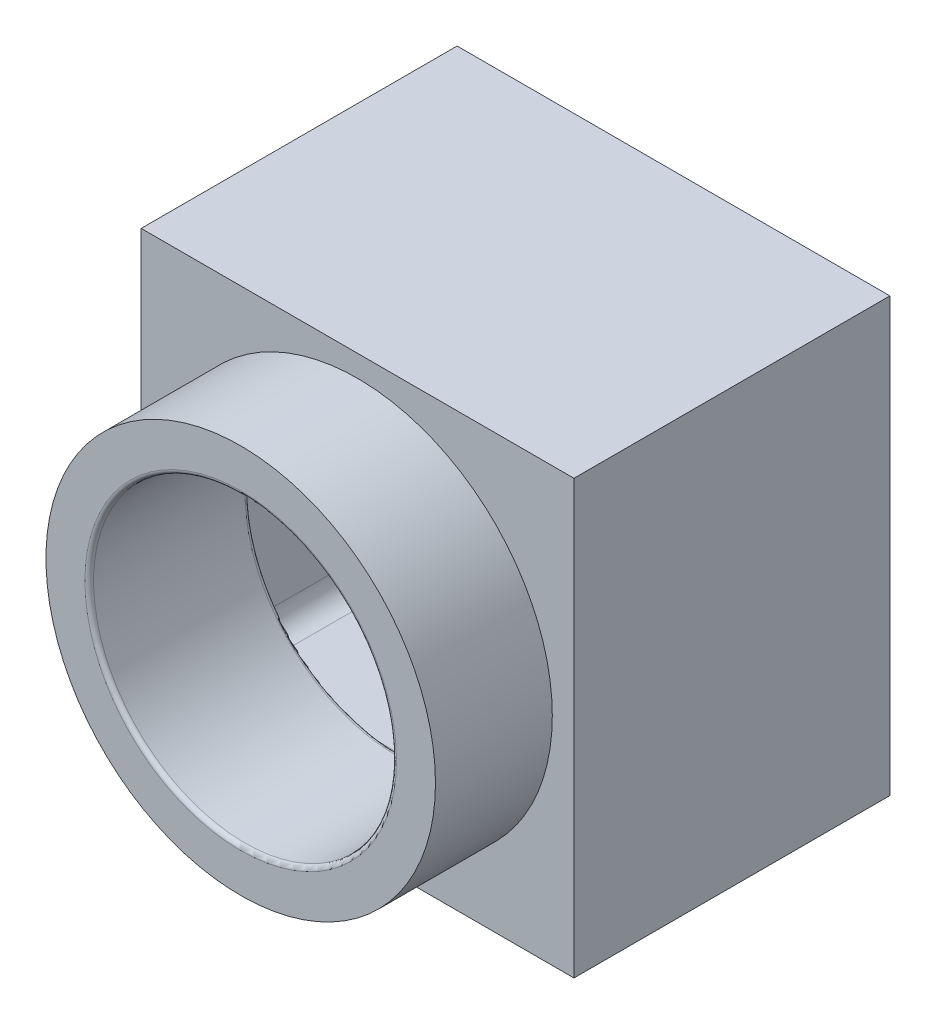
SolidWorks part; units mm, degrees
ref_plane "Front Plane" through (0, 0, 0) normal (0, 0, 1) x (1, 0, 0)
ref_plane "Top Plane" through (0, 0, 0) normal (0, 1, 0) x (1, 0, 0)
ref_plane "Right Plane" through (0, 0, 0) normal (1, 0, 0) x (0, 0, -1)
sketch "Sketch1" plane through (0, 0, 0) normal (0, 0, 1) x (1, 0, 0)
  line L1 (-12.7, 12.7) -> (12.7, 12.7)
  line L2 (-12.7, 12.7) -> (-12.7, -12.7)
  line L3 (-12.7, -12.7) -> (12.7, -12.7)
  line L4 (12.7, 12.7) -> (12.7, -12.7)
  line L5 (-12.7, 12.7) -> (12.7, -12.7) construction
  dimension "D1" = 25.4
  dimension "D2" = 25.4
extrude "Boss-Extrude1" add sketch "Sketch1" against normal blind 25.4
ref_plane "Plane1" through (0, 0, -9.398) normal (0, 0, 1) x (1, 0, 0)
sketch "Sketch2" plane through (0, 0, -9.398) normal (0, 0, 1) x (1, 0, 0)
  line L0 (-11.2268, 10.2235) -> (11.2268, -10.2235) construction
  line L1 (-11.2268, 10.2235) -> (11.2268, 10.2235)
  line L2 (-11.2268, 10.2235) -> (-11.2268, -10.2235)
  line L3 (-11.2268, -10.2235) -> (11.2268, -10.2235)
  line L4 (11.2268, 10.2235) -> (11.2268, -10.2235)
  point P4 (0, 0)
  dimension "D1" = 22.4536
  dimension "D2" = 20.447
extrude "Cut-Extrude1" cut sketch "Sketch2" against normal through all
sketch "Sketch3" plane through (0, 0, 0) normal (0, 0, 1) x (1, 0, 0)
  circle A0 centre (0, 0) radius 8.89
  dimension "D1" = 17.78
extrude "Cut-Extrude2" cut sketch "Sketch3" against normal through all both and the other way through all
ref_plane "Plane2" through (0, 0, -6.858) normal (0, 0, 1) x (1, 0, 0)
sketch "Sketch4" plane through (0, 0, -6.858) normal (0, 0, 1) x (1, 0, 0)
  circle A0 centre (0, 0) radius 8.89 construction
  circle A1 centre (0, 0) radius 8.89 construction
  circle A2 centre (0, 0) radius 11.43
  circle A3 centre (0, 0) radius 63.5
  dimension "D2" = 127
  dimension "D1" = 2.54
extrude "Cut-Extrude3" cut sketch "Sketch4" along normal through all
fillet "Fillet1" radius 1.27 4 edges at (0, -10.2235, -9.398) (11.2268, 0, -9.398) (0, 10.2235, -9.398) (-11.2268, 0, -9.398)
fillet "Fillet2" radius 1.27 8 edges at (-10.8548, -9.8515, -9.77) (-10.8548, 9.8515, -9.77) (10.8548, 9.8515, -9.77) (10.8548, -9.8515, -9.77) (-11.2268, -10.2235, -18.034) (-11.2268, 10.2235, -18.034) (11.2268, 10.2235, -18.034) (11.2268, -10.2235, -18.034)
fillet "Fillet3" radius 0.254 2 edges at (8.89, 0, -9.398) (8.89, 0, 0)
